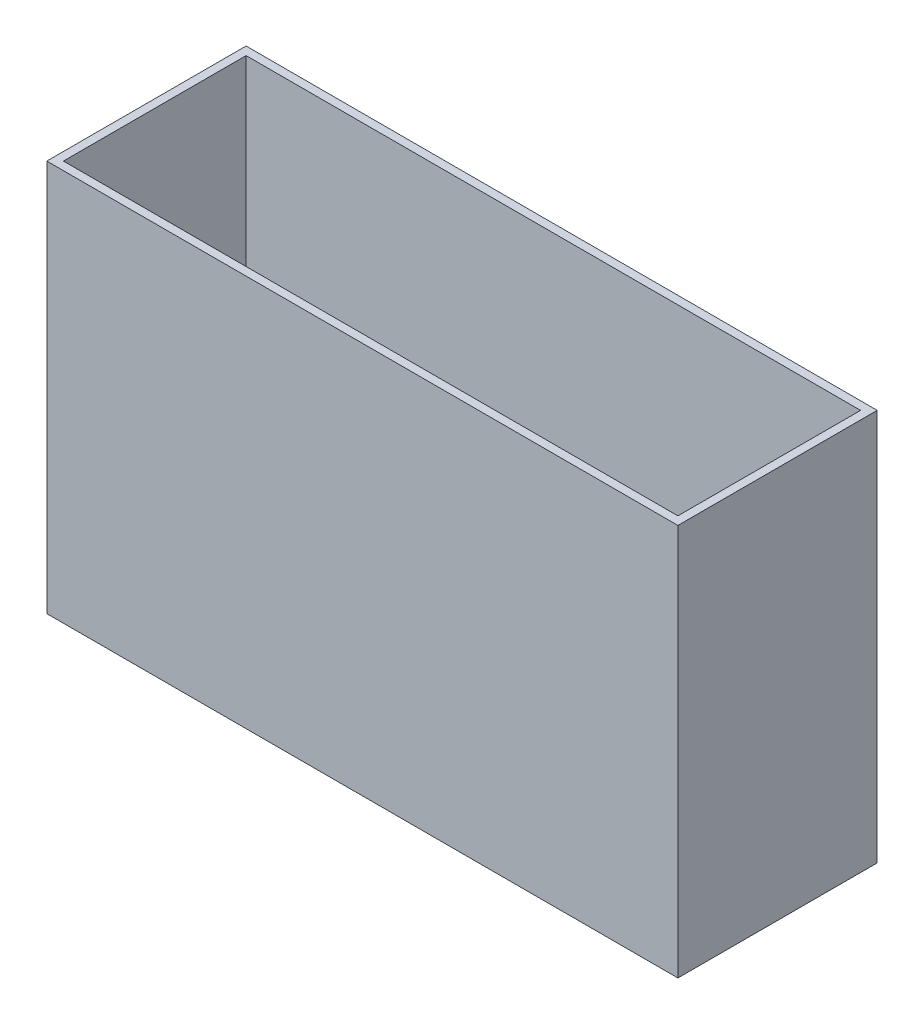
SolidWorks part; units mm, degrees
ref_plane "Front" through (0, 0, 0) normal (0, 0, 1) x (1, 0, 0)
ref_plane "Top" through (0, 0, 0) normal (0, 1, 0) x (1, 0, 0)
ref_plane "Right" through (0, 0, 0) normal (1, 0, 0) x (0, 0, -1)
sketch "Sketch1" plane through (0, 0, 0) normal (0, 1, 0) x (1, 0, 0)
  line L1 (-120.65, 38.1) -> (120.65, 38.1)
  line L2 (-120.65, 38.1) -> (-120.65, -38.1)
  line L3 (-120.65, -38.1) -> (120.65, -38.1)
  line L4 (120.65, 38.1) -> (120.65, -38.1)
  line L5 (-120.65, 38.1) -> (120.65, -38.1) construction
  line L6 (-120.65, -38.1) -> (120.65, 38.1) construction
  line L7 (-102.87, 2.794) -> (102.87, 2.794)
  line L8 (-102.87, 2.794) -> (-102.87, -2.794)
  line L9 (-102.87, -2.794) -> (102.87, -2.794)
  line L10 (102.87, 2.794) -> (102.87, -2.794)
  line L11 (-102.87, 2.794) -> (102.87, -2.794) construction
  line L12 (-102.87, -2.794) -> (102.87, 2.794) construction
  point P0 (0, 0)
  point P6 (0, 0)
  point P7 (0, 0)
  dimension "D1" = 241.3
  dimension "D2" = 76.2
  dimension "D3" = 5.588
  dimension "D4" = 205.74
extrude "Boss-Extrude1" add sketch "Sketch1" along normal blind 149.86
shell "Shell1" thickness 3.175 removed face at (0, 0, 0) removed face at (0, 74.93, -2.794) removed face at (0, 74.93, 2.794) removed face at (-102.87, 74.93, 0) removed face at (102.87, 74.93, 0) removed face at (0, 149.86, 0)
equation "\"0.1025n\"=0.1"
